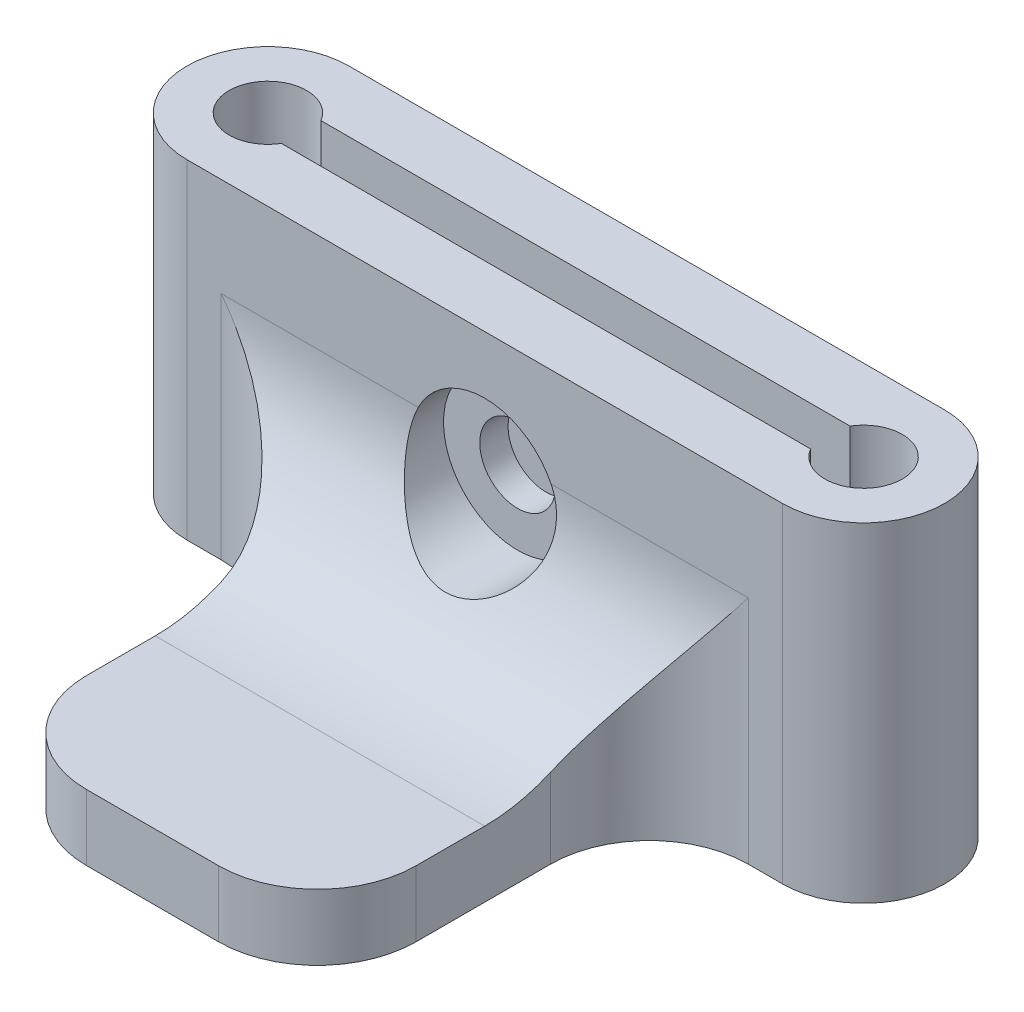
SolidWorks part; units mm, degrees
ref_plane "前视基准面" through (0, 0, 0) normal (0, 0, 1) x (1, 0, 0)
ref_plane "上视基准面" through (0, 0, 0) normal (0, 1, 0) x (1, 0, 0)
ref_plane "右视基准面" through (0, 0, 0) normal (1, 0, 0) x (0, 0, -1)
sketch "草图1" plane through (0, 0, 0) normal (0, 1, 0) x (1, 0, 0)
  line L0 (0, 0) -> (0, 4.7348) construction
  line L1 (0, 0) -> (9.04, 0) construction
  line L2 (-9.04, 0) -> (9.04, 0) construction
  line L3 (-6.4249, 17.0648) -> (6.4249, 17.0648) construction
  line L4 (-6.4249, 17.0648) -> (-6.4249, 3.25) construction
  line L5 (-6.4249, 3.25) -> (6.4249, 3.25) construction
  line L6 (6.4249, 17.0648) -> (6.4249, 3.25) construction
  line L7 (-6.4249, 17.0648) -> (6.4249, 3.25) construction
  line L8 (-6.4249, 3.25) -> (6.4249, 17.0648) construction
  line L9 (-9.04, 2.46) -> (9.04, 2.46)
  line L10 (-9.04, -2.46) -> (9.04, -2.46)
  circle A0 centre (0, 0) radius 11.5 construction
  circle A1 centre (9.04, 0) radius 1.175
  circle A2 centre (-9.04, 0) radius 1.175
  arc A3 (-9.04, 2.46) -> (-9.04, -2.46) centre (-9.04, 0) ccw
  arc A4 (9.04, -2.46) -> (9.04, 2.46) centre (9.04, 0) ccw
  point P8 (0, 10.1574)
  point P13 (0, 0)
  dimension "D1" = 23
  dimension "D3" = 2.35
  dimension "D2" = 18.08
  dimension "D4" = 3.25
extrude "凸台-拉伸1" add sketch "草图1" along normal blind 10
sketch "草图3" plane through (0, 0, 0) normal (0, -1, 0) x (1, 0, 0)
  line L0 (0, 0) -> (0, 5.04) construction
  line L1 (9.04, -2.46) -> (-9.04, -2.46) construction
  line L2 (-5, 12.54) -> (5, 12.54)
  line L3 (-5, 12.54) -> (-5, -2.46)
  line L4 (-5, -2.46) -> (5, -2.46)
  line L5 (5, 12.54) -> (5, -2.46)
  line L6 (-5, 12.54) -> (5, -2.46) construction
  line L7 (-5, -2.46) -> (5, 12.54) construction
  dimension "D1" = 10
  dimension "D2" = 15
extrude "凸台-拉伸2" add sketch "草图3" against normal blind 2
chamfer "倒角2" [suppressed] distance 10 angle 45
fillet "圆角2" radius 3 4 edges at (-5, 1, 12.54) (5, 1, 12.54) (5, 1, 2.46) (-5, 1, 2.46)
fillet "圆角3" radius 5 1 edges at (0, 2, 2.46)
sketch "草图4" plane through (0, 0, 0) normal (0, -1, 0) x (1, 0, 0)
  line L1 (-8.0297, -0.6) -> (8.0297, -0.6)
  line L2 (-8.0297, -0.6) -> (-8.0297, 0.6)
  line L3 (-8.0297, 0.6) -> (8.0297, 0.6)
  line L4 (8.0297, -0.6) -> (8.0297, 0.6)
  line L5 (-8.0297, -0.6) -> (8.0297, 0.6) construction
  line L6 (-8.0297, 0.6) -> (8.0297, -0.6) construction
  circle A0 centre (9.04, 0) radius 1.175 construction
  point P0 (0, 0)
  dimension "D1" = 1.2
extrude "切除-拉伸2" cut sketch "草图4" against normal through all
sketch "草图6" plane through (0, 0, 2.46) normal (0, 0, 1) x (1, 0, 0)
  line L0 (0, 0) -> (0, 6) construction
  line L1 (-9.04, 10) -> (9.04, 10) construction
  circle A0 centre (0, 6) radius 2.25
  dimension "D1" = 4.5
  dimension "D2" = 4
extrude "切除-拉伸4" cut sketch "草图6" against normal blind 1 and the other way through all
sketch "草图7" plane through (0, 0, 1.46) normal (0, 0, 1) x (1, 0, 0)
  circle A0 centre (0, 6) radius 1.15
  dimension "D1" = 2.3
extrude "切除-拉伸5" cut sketch "草图7" against normal through all
sketch "草图8" plane through (0, 0, -2.46) normal (0, 0, -1) x (-1, 0, 0)
  line L0 (0, 8.4249) -> (0, 6) construction
  line L1 (0, 8.4249) -> (-2.1, 7.2124)
  line L2 (-2.1, 7.2124) -> (-2.1, 4.7876)
  line L3 (-2.1, 4.7876) -> (0, 3.5751)
  line L4 (0, 3.5751) -> (2.1, 4.7876)
  line L5 (2.1, 4.7876) -> (2.1, 7.2124)
  line L6 (2.1, 7.2124) -> (0, 8.4249)
  circle A0 centre (0, 6) radius 1.15 construction
  circle A1 centre (0, 6) radius 1.15 construction
  circle A2 centre (0, 6) radius 2.1 construction
  dimension "D1" = 4.2
extrude "切除-拉伸6" cut sketch "草图8" against normal blind 1
